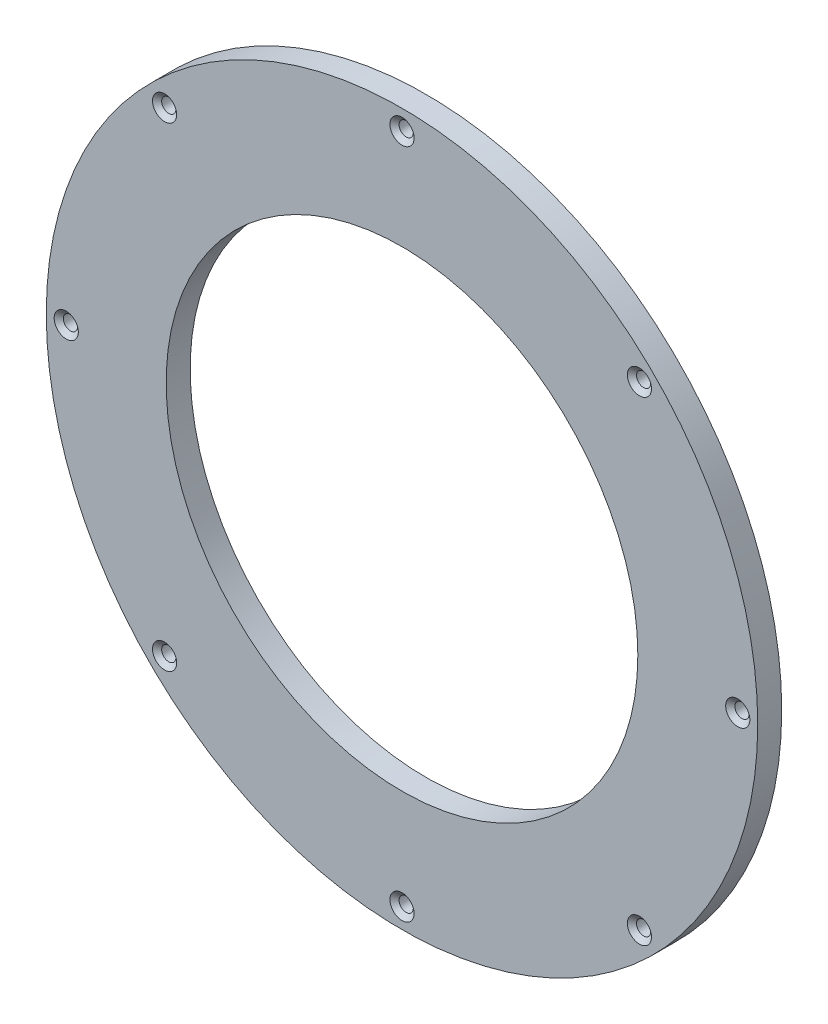
SolidWorks part; units mm, degrees
ref_plane "Front Plane" through (0, 0, 0) normal (0, 0, 1) x (1, 0, 0)
ref_plane "Top Plane" through (0, 0, 0) normal (0, 1, 0) x (1, 0, 0)
ref_plane "Right Plane" through (0, 0, 0) normal (1, 0, 0) x (0, 0, -1)
sketch "Sketch1" plane through (0, 0, 0) normal (0, 0, 1) x (1, 0, 0)
  circle A0 centre (0, 0) radius 44.5
  dimension "D1" = 89
extrude "Boss-Extrude1" add sketch "Sketch1" along normal blind 3
sketch "Sketch2" plane through (0, 0, 3) normal (0, 0, 1) x (1, 0, 0)
  circle A0 centre (0, 0) radius 29.5
  circle A1 centre (0, 0) radius 44.5 construction
  dimension "D1" = 15
extrude "Cut-Extrude1" cut sketch "Sketch2" against normal up to surface (3 mm away) up to face at (44.5, 0, 0)
hole_wizard "CSK for #0 Flat Head Machine Screw (100)1" positions "Sketch3" profile "Sketch4" countersink size "#0" standard "ANSI Inch" end condition through all
sketch "Sketch3" plane through (0, 0, 3) normal (0, 0, 1) x (1, 0, 0)
  circle A0 centre (0, 0) radius 44.5 construction
  point P0 (0, 42)
  dimension "D1" = 42
sketch "Sketch4" plane through (0, 42, 3) normal (1, 0, 0) x (0, -1, 0)
  line L0 (0, 0) -> (0, 3)
  line L1 (0, 3) -> (0.889, 3)
  line L2 (0.889, 3) -> (0.889, 0.5222)
  line L3 (0.889, 0.5222) -> (1.5113, 0)
  line L5 (1.5113, 0) -> (0, 0)
  line L6 (-0.889, 0.5222) -> (-1.5113, 0) construction
  line L11 (0, -6.35) -> (0, 107.95) construction
  dimension "Thru Hole Dia." = 1.778
  dimension "Thru Hole Depth" = 3
  dimension "Near C'Sink Dia." = 3.0226
  dimension "Near C'Sink Angle" = 100
pattern_circular "CirPattern1" count 8 over 360 about axis through (0, 0, 3) along (0, 0, 1) of "CSK for #0 Flat Head Machine Screw (100)1"
scale "Scale1" scale about centroid uniform scaling yes scale factor 0.5
